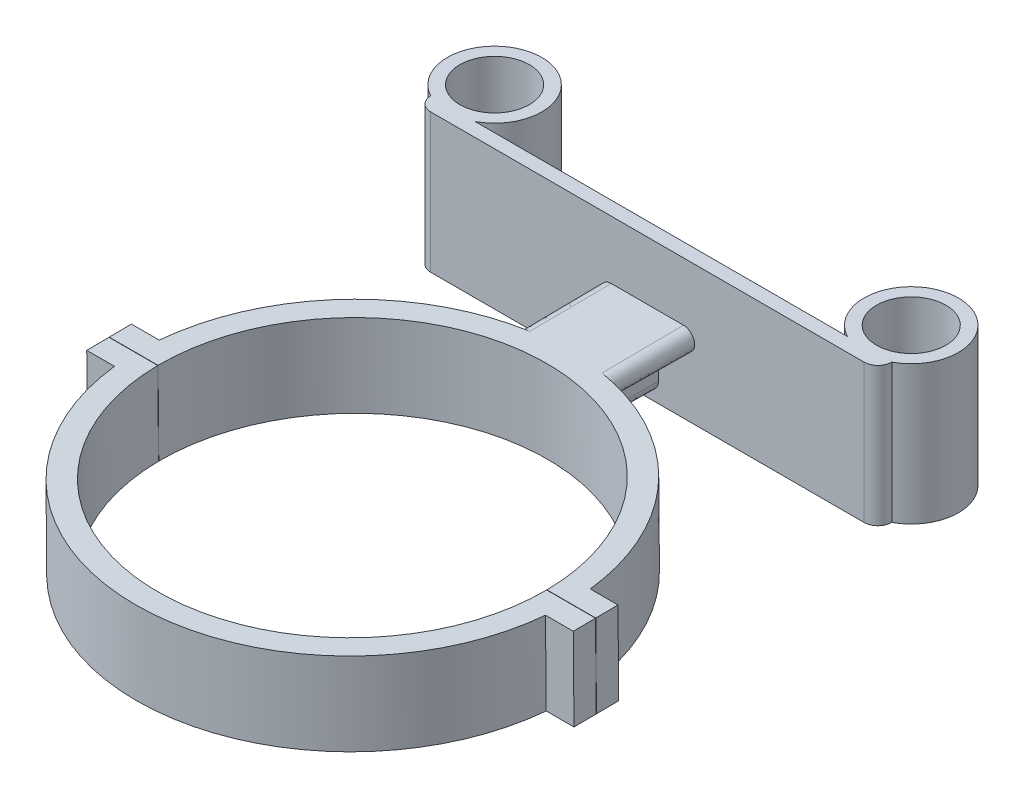
SolidWorks part; units mm, degrees
material "Полиэтилен ВД ГОСТ 16337-77"
ref_plane "Спереди" through (0, 0, 0) normal (0, 0, 1) x (1, 0, 0)
ref_plane "Сверху" through (0, 0, 0) normal (0, 1, 0) x (1, 0, 0)
ref_plane "Справа" through (0, 0, 0) normal (1, 0, 0) x (0, 0, -1)
ref_axis "ОсьX" through (-88.99, 0, 0) along (1, 0, 0)
ref_axis "ОсьZ" through (0, 55, 0) along (0, -1, 0)
ref_axis "ОсьY" through (0, 0, -88.99) along (0, 0, 1)
sketch "Эскиз1" plane through (0, 0, 0) normal (0, 0, 1) x (1, 0, 0)
  line L0 (-13.7709, 0) -> (0, 0) construction
  line L1 (-83, 25) -> (83, 25)
  line L2 (-83, 25) -> (-83, -25)
  line L3 (-83, -25) -> (83, -25)
  line L4 (83, 25) -> (83, -25)
  line L5 (0, 0) -> (0, 15.6102) construction
  point P4 (-83, 0)
  point P6 (0, 25)
  dimension "D1" = 166
  dimension "D2" = 50
extrude "Бобышка-Вытянуть1" add sketch "Эскиз1" along normal blind 5
sketch "Эскиз4" plane through (0, 0, 0) normal (0, 1, 0) x (1, 0, 0)
  line L0 (0, -3.31) -> (0, 24.236) construction
  line L1 (-83, 0) -> (-67, 0)
  line L2 (83, 0) -> (-83, 0) construction
  line L3 (83, 0) -> (67, 0)
  circle A0 centre (-75, 15) radius 12.5
  arc A1 (-67, 0) -> (-83, 0) centre (-75, 15) ccw
  arc A2 (67, 0) -> (83, 0) centre (75, 15) cw
  circle A3 centre (75, 15) radius 12.5
  dimension "D1" = 25
  dimension "D2" = 17
  dimension "D3" = 15
  dimension "D4" = 150
extrude "Бобышка-Вытянуть4" add sketch "Эскиз4" along normal up to surface and the other way up to surface up to face at (0, 25, 2.5) other way up to face at (0, -25, 2.5)
fillet "Скругление1" radius 5 2 edges at (83, 0, 5) (-83, 0, 5)
sketch "Эскиз2" plane through (0, 0, 5) normal (0, 0, 1) x (1, 0, 0)
  line L0 (-13, 0) -> (13, 0) construction
  line L1 (-13, 4) -> (13, 4)
  line L2 (-13, -4) -> (-5, -4)
  line L3 (0, -4) -> (0, -18) construction
  line L4 (4, -5) -> (4, -18)
  line L5 (-4, -5) -> (-4, -18)
  line L6 (5, -4) -> (13, -4)
  arc A0 (-13, 4) -> (-13, -4) centre (-13, 0) ccw
  arc A1 (13, -4) -> (13, 4) centre (13, 0) ccw
  arc A3 (-4, -18) -> (4, -18) centre (0, -18) ccw
  arc A4 (4, -5) -> (5, -4) centre (5, -5) cw
  arc A5 (-4, -5) -> (-5, -4) centre (-5, -5) ccw
  point P2 (0, 0)
  point P7 (0, -7.5)
  dimension "D2" = 30
  dimension "D3" = 22
  dimension "D4" = 1
  dimension "D1" = 8
extrude "Бобышка-Вытянуть2" add sketch "Эскиз2" along normal blind 30 draft 0.5
sketch "Эскиз3" plane through (0, 4.0433, 0.0353) normal (0, 1, 0.0087) x (1, 0, 0)
  line L0 (70, -111.1316) -> (87.5835, -111.1316)
  line L1 (-87.5835, -111.1316) -> (-70, -111.1316)
  line L3 (-87.5835, -111.2316) -> (-70, -111.2316)
  line L5 (70, -111.2316) -> (87.5835, -111.2316)
  line L6 (-13.7929, -111.1816) -> (8.3285, -111.1816) construction
  line L8 (-87.5835, -111.1316) -> (-87.5835, -103.1316)
  line L9 (-87.5835, -103.1316) -> (-77.5835, -103.1316)
  line L10 (0, -111.1816) -> (0, -255.6089) construction
  line L11 (-87.5835, -111.2316) -> (-87.5835, -119.2316)
  line L12 (-87.5835, -119.2316) -> (-77.5835, -119.2316)
  line L13 (87.5835, -119.2316) -> (77.5835, -119.2316)
  line L14 (87.5835, -111.2316) -> (87.5835, -119.2316)
  line L15 (87.5835, -111.1316) -> (87.5835, -103.1316)
  line L16 (87.5835, -103.1316) -> (77.5835, -103.1316)
  arc A0 (-77.5835, -119.2316) -> (77.5835, -119.2316) centre (0, -111.1816) ccw
  arc A1 (-70, -111.2316) -> (70, -111.2316) centre (0, -111.1816) ccw
  arc A2 (70, -111.1316) -> (-70, -111.1316) centre (0, -111.1816) ccw
  circle A3 centre (0, -111.1816) radius 78 construction
  circle A4 centre (0, -111.1816) radius 70 construction
  arc A5 (77.5835, -103.1316) -> (-77.5835, -103.1316) centre (0, -111.1816) ccw
  point P1 (36.3396, -238.7245)
  point P9 (43.99, -236.3855)
  dimension "D2" = 140
  dimension "D3" = 0.1
  dimension "D4" = 8
  dimension "D5" = 10
  dimension "D1" = 8
extrude "Бобышка-Вытянуть3" add sketch "Эскиз3" against normal blind 30
